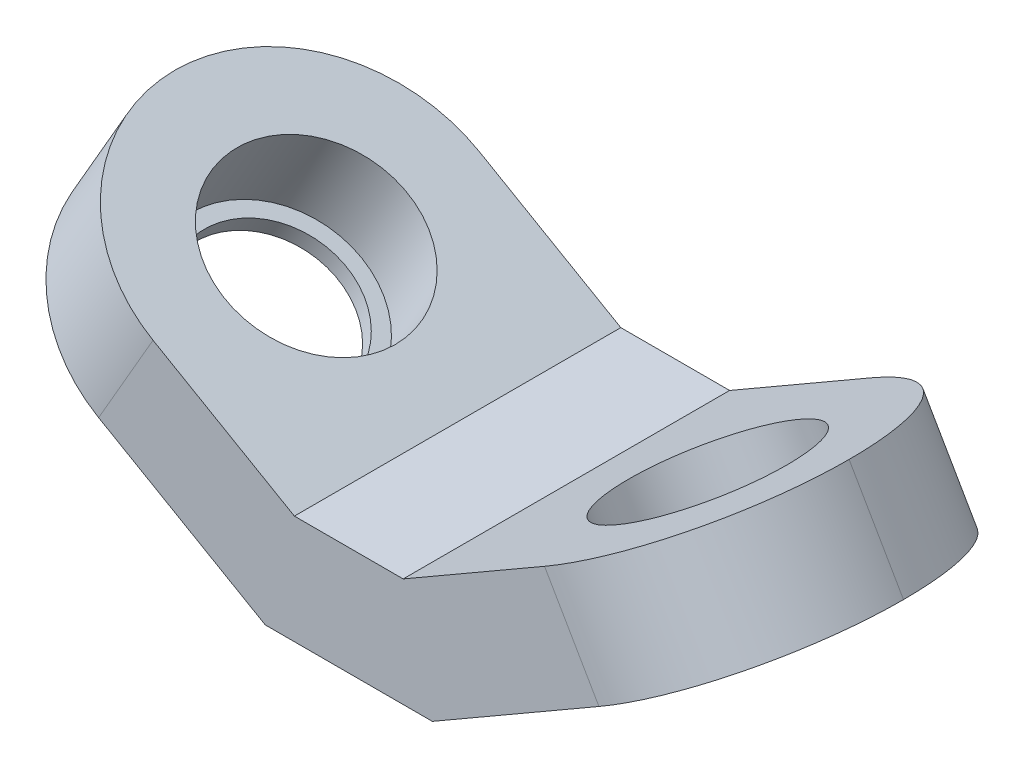
SolidWorks part; units mm, degrees
ref_plane "正面" through (0, 0, 0) normal (0, 0, 1) x (1, 0, 0)
ref_plane "平面" through (0, 0, 0) normal (0, 1, 0) x (1, 0, 0)
ref_plane "右側面" through (0, 0, 0) normal (1, 0, 0) x (0, 0, -1)
sketch "ｽｹｯﾁ1" plane through (0, 0, 0) normal (0, 0, 1) x (1, 0, 0)
  line L0 (0, 0) -> (-14.1506, 8.1699)
  line L1 (-14.1506, 8.1699) -> (-11.6506, 12.5)
  line L2 (-11.6506, 12.5) -> (1.3397, 5)
  line L3 (1.3397, 5) -> (6.3397, 5)
  line L4 (6.3397, 5) -> (19.3301, 12.5)
  line L5 (19.3301, 12.5) -> (21.8301, 8.1699)
  line L6 (21.8301, 8.1699) -> (7.6795, 0)
  line L7 (7.6795, 0) -> (0, 0)
  dimension "D1" = 150
  dimension "D2" = 150
  dimension "D3" = 5
  dimension "D4" = 5
  dimension "D5" = 5
  dimension "D6" = 15
  dimension "D7" = 15
  dimension "D8" = 5
extrude "ﾎﾞｽ - 押し出し1" add sketch "ｽｹｯﾁ1" along normal mid plane 15
sketch "ｽｹｯﾁ2" plane through (0, 0, 0) normal (-0.5, -0.866, 0) x (0, 0, 1)
  line L0 (7.5, 1.3397) -> (7.5, 16.3397) construction
  circle A0 centre (0, 8.8397) radius 4.2
  point P6 (7.5, 8.8397)
  dimension "D1" = 8.4
extrude "ｶｯﾄ - 押し出し1" cut sketch "ｽｹｯﾁ2" against normal through all both and the other way through all
sketch "ｽｹｯﾁ3" plane through (1.9199, -3.3253, 0) normal (0.5, -0.866, 0) x (0, 0, -1)
  line L0 (-7.5, 22.9904) -> (-7.5, 7.9904) construction
  line L1 (-7.5, 22.9904) -> (7.5, 22.9904) construction
  circle A0 centre (0, 15.4904) radius 4.2
  point P4 (-7.5, 15.4904)
  point P7 (0, 22.9904)
  dimension "D1" = 8.4
extrude "ｶｯﾄ - 押し出し2" cut sketch "ｽｹｯﾁ3" against normal through all both and the other way through all
fillet "ﾌｨﾚｯﾄ1" radius 7.5 4 edges at (20.5801, 10.3349, -7.5) (20.5801, 10.3349, 7.5) (-12.9006, 10.3349, -7.5) (-12.9006, 10.3349, 7.5)
sketch "ｽｹｯﾁ4" plane through (0, 0, 0) normal (0.5, 0.866, 0) x (0.866, -0.5, 0)
  circle A0 centre (-8.8397, 0) radius 4.2 construction
  circle A1 centre (-8.8397, 0) radius 4.2
  circle A2 centre (-8.8397, 0) radius 3.5
  dimension "D1" = 7
extrude "ﾎﾞｽ - 押し出し2" add sketch "ｽｹｯﾁ4" along normal blind 0.8
sketch "ｽｹｯﾁ5" plane through (1.9199, -3.3253, 0) normal (-0.5, 0.866, 0) x (0.866, 0.5, 0)
  circle A0 centre (15.4904, 0) radius 4.2 construction
  circle A1 centre (15.4904, 0) radius 4.2
  circle A2 centre (15.4904, 0) radius 3.5
  dimension "D1" = 7
extrude "ﾎﾞｽ - 押し出し3" add sketch "ｽｹｯﾁ5" along normal blind 0.8
equation "\"D4@ｽｹｯﾁ1\"=\"D3@ｽｹｯﾁ1\""
equation "\"D5@ｽｹｯﾁ1\"=\"D3@ｽｹｯﾁ1\""
equation "\"D2@ｽｹｯﾁ1\"=\"D1@ｽｹｯﾁ1\""
